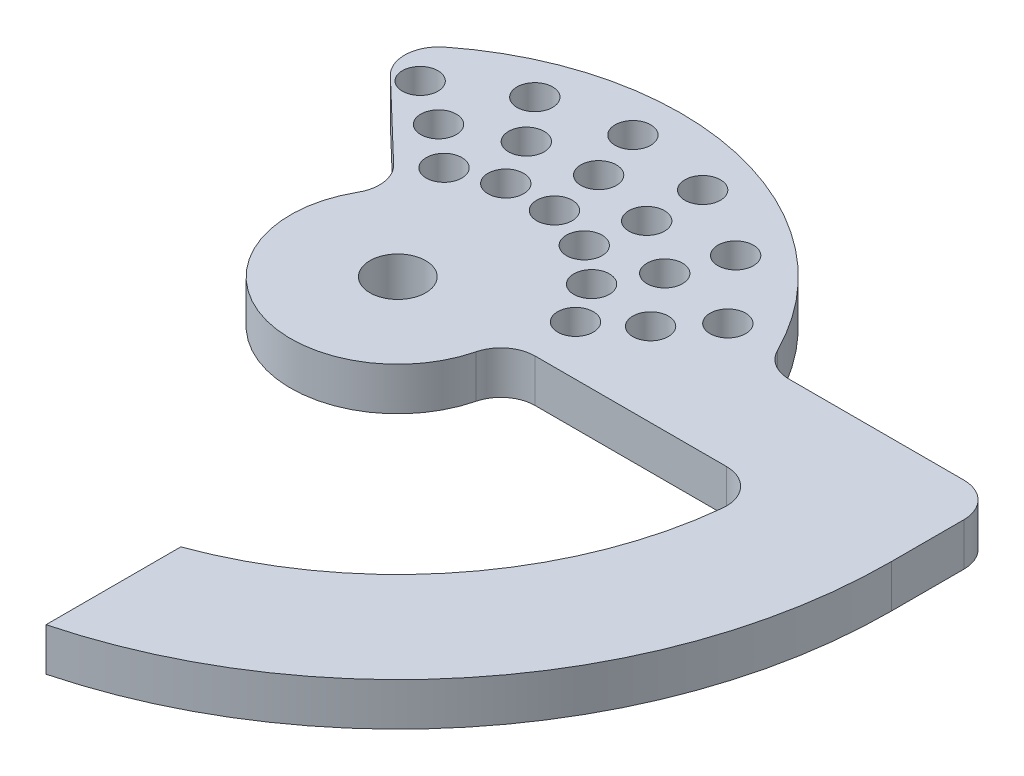
SolidWorks part; units mm, degrees
ref_plane "Front Plane" through (0, 0, 0) normal (0, 0, 1) x (1, 0, 0)
ref_plane "Top Plane" through (0, 0, 0) normal (0, 1, 0) x (1, 0, 0)
ref_plane "Right Plane" through (0, 0, 0) normal (1, 0, 0) x (0, 0, -1)
sketch "Sketch1" plane through (0, 0, 0) normal (0, 1, 0) x (1, 0, 0)
  circle A0 centre (0, 0) radius 12.5
  dimension "D1" = 25
extrude "Boss-Extrude1" add sketch "Sketch1" along normal blind 5
sketch "Sketch4" plane through (0, 0, 0) normal (0, 1, 0) x (1, 0, 0)
  line L0 (0, 0) -> (50, 0) construction
  line L1 (0, 0) -> (14.6186, -47.8152) construction
  arc A0 (14.6186, -47.8152) -> (50, 0) centre (0, 0) ccw
  dimension "D2" = 73
  dimension "D3" = 50
extrude "Extrude-Thin1" add sketch "Sketch4" along normal blind 5 separate body thin thin type mid plane wall 15
sketch "Sketch6" plane through (0, 0, 0) normal (0, 1, 0) x (1, 0, 0)
  line L1 (57.5, 0) -> (1, 0)
  line L2 (57.5, 0) -> (57.5, 12.4599)
  line L3 (57.5, 12.4599) -> (1, 12.4599)
  line L4 (1, 0) -> (1, 12.4599)
  line L5 (29.25, 12.4599) -> (29.25, 0) construction
  line L6 (57.5, 6.23) -> (1, 6.23) construction
  circle A0 centre (0, 0) radius 12.5 construction
  point P104 (29.25, 6.23)
extrude "Boss-Extrude3" add sketch "Sketch6" along normal up to surface (5 mm away) up to face at (0, 5, 12.5)
sketch "Sketch7" plane through (0, 5, 0) normal (0, 1, 0) x (1, 0, 0)
  circle A0 centre (0, 0) radius 3.25
  dimension "D1" = 6.5
extrude "Cut-Extrude3" cut sketch "Sketch7" against normal through all both and the other way through all
sketch "Sketch9" plane through (0, 0, 0) normal (0, 1, 0) x (1, 0, 0)
  line L0 (16.8114, -54.9875) -> (12.4258, -40.643) construction
  line L1 (0, 0) -> (23.9434, 0) construction
  line L2 (12.5, 0) -> (42.5, 0) construction
  line L3 (14.6186, 0) -> (14.6186, -61.8648) construction
  line L4 (12.4258, -40.643) -> (11.863, -56.263)
  line L5 (14.6186, -37.5897) -> (4.9921, -37.5897)
  line L6 (14.6186, -37.5897) -> (14.6186, -60.7122)
  line L7 (14.6186, -60.7122) -> (4.9921, -60.7122)
  line L8 (4.9921, -37.5897) -> (4.9921, -60.7122)
  line L9 (9.8053, -60.7122) -> (9.8053, -37.5897) construction
  line L10 (14.6186, -49.151) -> (4.9921, -49.151) construction
  line L11 (16.8114, -54.9875) -> (12.4258, -40.643)
  arc A0 (16.8114, -54.9875) -> (11.863, -56.263) centre (0, 0) cw
  point P0 (14.6186, -47.8152)
  point P166 (9.8053, -49.151)
extrude "Boss-Extrude4" add sketch "Sketch9" along normal blind 5 contours A0 L11 L6 | A0 L6 L11 L4 region at (13.2318, 0, 50.04) region at (15.3502, 0, 52.8095)
extrude "Cut-Extrude5" cut sketch "Sketch9<4>" along normal through all contours L6 L7 L8 L5
sketch "Sketch9<4>" plane through (0, 0, 0) normal (0, 1, 0) x (1, 0, 0) same geometry as "Sketch9"
sketch "Sketch10" plane through (0, 0, 0) normal (0, 1, 0) x (1, 0, 0)
  line L0 (0, 0) -> (-23.8274, 22.8311) construction
  line L4 (-23.8274, 22.8311) -> (-5.9312, 5.6832)
  line L6 (31.686, 9.2196) -> (0, 0) construction
  line L7 (31.686, 9.2196) -> (19.5321, 5.6832)
  line L8 (19.5321, 5.6832) -> (-5.9312, 5.6832)
  arc A0 (-23.8274, 22.8311) -> (31.686, 9.2196) centre (0, 0) cw
  dimension "D1" = 33
  dimension "D2" = 120
extrude "Boss-Extrude5" add sketch "Sketch10" along normal up to surface (5 mm away) up to face at (28.5796, 5, 13.8571)
sketch "Sketch11" plane through (0, 5, 0) normal (0, 1, 0) x (1, 0, 0)
  line L0 (0, 0) -> (-17.1064, 28.2201) construction
  line L1 (-23.8274, 22.8311) -> (-9.0255, 8.6481) construction
  arc A0 (30.5573, 12.4599) -> (-23.8274, 22.8311) centre (0, 0) ccw construction
  circle A2 centre (-8.294, 13.6825) radius 2.075
  dimension "D2" = 4.15
  dimension "D4" = 16
  dimension "D5" = 15
extrude "Cut-Extrude6" cut sketch "Sketch11" against normal through all
sketch "Sketch12" plane through (0, 5, 0) normal (0, 1, 0) x (1, 0, 0)
  line L0 (0, 0) -> (-17.1064, 28.2201) construction
  line L1 (-23.8274, 22.8311) -> (-9.0255, 8.6481) construction
  line L2 (0, 0) -> (-19.5008, 26.6218) construction
  arc A0 (30.5573, 12.4599) -> (-23.8274, 22.8311) centre (0, 0) ccw construction
  circle A1 centre (-13.0005, 17.7478) radius 2.075
  point P11 (-9.4549, 12.9075)
  dimension "D3" = 6
  dimension "D4" = 4.15
  dimension "D1" = 15
  dimension "D2" = 16
  dimension "D5" = 5
extrude "Cut-Extrude7" cut sketch "Sketch12" against normal through all
sketch "Sketch13" plane through (0, 5, 0) normal (0, 1, 0) x (1, 0, 0)
  line L0 (0, 0) -> (-17.1064, 28.2201) construction
  line L1 (0, 0) -> (-21.7468, 24.8209) construction
  line L2 (-23.8274, 22.8311) -> (-9.0255, 8.6481) construction
  arc A0 (30.5573, 12.4599) -> (-23.8274, 22.8311) centre (0, 0) ccw construction
  circle A1 centre (-18.4519, 21.0601) radius 2.075
  point P9 (-14.4979, 16.5472)
  dimension "D3" = 4.15
  dimension "D5" = 6
  dimension "D1" = 15
  dimension "D2" = 10
  dimension "D4" = 22
extrude "Cut-Extrude8" cut sketch "Sketch13" against normal through all
pattern_circular "CirPattern1" count 6 every 20 about axis through (0, 5, 0) along (0, 1, 0) of "Cut-Extrude6" reverse direction yes
pattern_circular "CirPattern2" count 6 every 20 about axis through (0, 5, 0) along (0, 1, 0) of "Cut-Extrude7" reverse direction yes
pattern_circular "CirPattern3" count 6 every 20 about axis through (0, 5, 0) along (0, 1, 0) of "Cut-Extrude8" reverse direction yes
fillet "Fillet2" radius 4 6 edges at (12.5, 2.5, 0) (57.5, 2.5, -12.4599) (42.5, 2.5, 0) (30.5573, 2.5, -12.4599) (-23.8274, 2.5, -22.8311) (-9.0255, 2.5, -8.6481)
